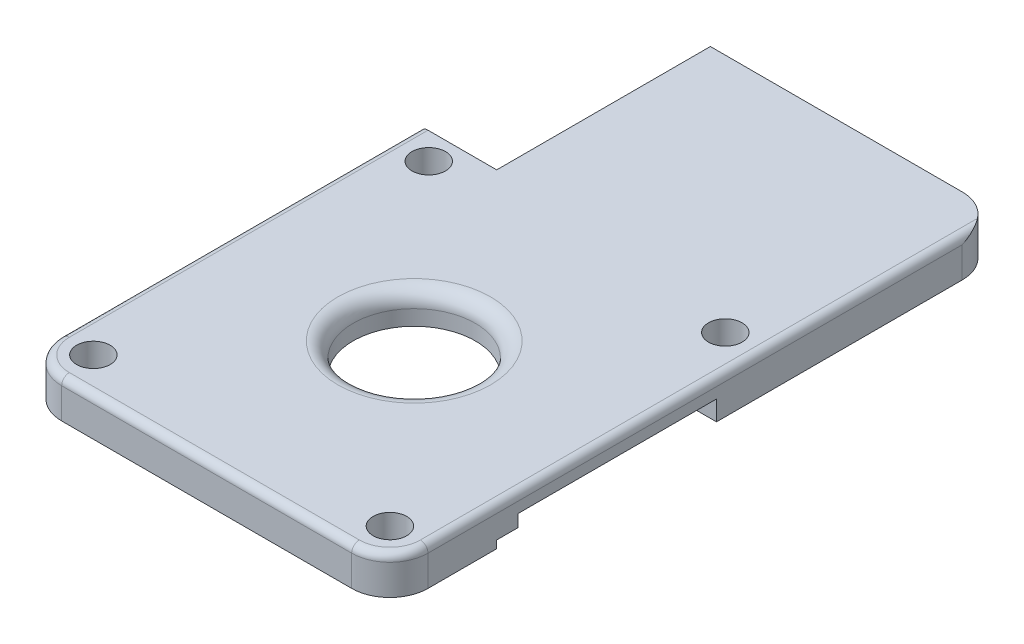
SolidWorks part; units mm, degrees
ref_plane "前视基准面" through (0, 0, 0) normal (0, 0, 1) x (1, 0, 0)
ref_plane "上视基准面" through (0, 0, 0) normal (0, 1, 0) x (1, 0, 0)
ref_plane "右视基准面" through (0, 0, 0) normal (1, 0, 0) x (0, 0, -1)
sketch "草图1" plane through (0, 0, 0) normal (0, 1, 0) x (1, 0, 0)
  line L0 (-12, 10.776) -> (-12, 24.224)
  line L18 (-9.5, 13.276) -> (9.5, 13.276) construction
  line L19 (-12, 10.776) -> (-12, -10.776)
  line L20 (-9.5, -13.276) -> (9.5, -13.276)
  line L21 (12, 10.776) -> (12, -10.776)
  line L22 (-12, 13.276) -> (12, -13.276) construction
  line L23 (-12, -13.276) -> (12, 13.276) construction
  line L24 (-9.5, 26.724) -> (9.5, 26.724)
  line L25 (12, 24.224) -> (12, 10.776)
  line L26 (-19.3805, 0) -> (19.2101, 0) construction
  line L27 (0, 33.0534) -> (0, -22.2948) construction
  line L37 (-9.715, 10.985) -> (9.715, -10.985) construction
  line L38 (-9.715, -10.985) -> (9.715, 10.985) construction
  line L39 (-9.714, 10.986) -> (9.714, 10.986) construction
  line L40 (-9.714, 10.986) -> (-9.714, -10.986) construction
  line L41 (-9.714, -10.986) -> (9.714, -10.986) construction
  line L42 (9.714, 10.986) -> (9.714, -10.986) construction
  line L43 (-9.714, 10.986) -> (9.714, -10.986) construction
  line L44 (-9.714, -10.986) -> (9.714, 10.986) construction
  arc A4 (-9.5, 13.276) -> (-12, 10.776) centre (-9.5, 10.776) ccw construction
  arc A5 (-9.5, -13.276) -> (-12, -10.776) centre (-9.5, -10.776) cw
  arc A6 (9.5, -13.276) -> (12, -10.776) centre (9.5, -10.776) ccw
  arc A7 (12, 10.776) -> (9.5, 13.276) centre (9.5, 10.776) ccw construction
  arc A8 (12, 24.224) -> (9.5, 26.724) centre (9.5, 24.224) ccw
  arc A9 (-12, 24.224) -> (-9.5, 26.724) centre (-9.5, 24.224) cw
  circle A12 centre (-9.714, -10.986) radius 2.2002
  circle A13 centre (-9.714, -10.986) radius 1.1
  circle A14 centre (9.714, -10.986) radius 1.1
  circle A15 centre (9.714, -10.986) radius 2.2002
  circle A16 centre (9.714, 10.986) radius 2.2002
  circle A17 centre (9.714, 10.986) radius 1.1
  circle A18 centre (-9.714, 10.986) radius 1.1
  circle A19 centre (-9.714, 10.986) radius 2.2002
  circle A20 centre (0, 0.32) radius 4
  point P0 (0, 0)
  point P28 (0, 0)
  point P34 (0, 0)
  dimension "D5" = 40
  dimension "D6" = 2.5
  dimension "D7" = 19.428
  dimension "D8" = 21.972
  dimension "D3" = 2.5
  dimension "D4" = 2.5
  dimension "D9" = 13.596
  dimension "D1" = 24
  dimension "D2" = 26.552
extrude "凸台-拉伸1" add sketch "草图1" against normal blind 2.5 contours A6 A15 L21 L25 A8 L24 A9 L0 L19 A5 A12 L20 A20 A16 A19 | A16 A17 | A19 A18 | A12 A13 | A15 A14
sketch "草图2" plane through (12, 0, 0) normal (1, 0, 0) x (0, 0, -1)
  line L0 (24.224, -2.5) -> (-10.776, -2.5) construction
  line L1 (-6.276, -2.5) -> (8.124, -2.5)
  line L2 (-6.276, -2.5) -> (-6.276, -2)
  line L3 (-6.276, -2) -> (8.124, -2)
  line L4 (8.124, -2.5) -> (8.124, -2)
  line L5 (-13.276, -2.5) -> (-13.276, 0) construction
  point P8 (8.124, -2.25)
  dimension "D1" = 21.4
  dimension "D2" = 7
  dimension "D3" = 0.5
extrude "切除-拉伸1" cut sketch "草图2" against normal through all
sketch "草图3" plane through (12, 0, 0) normal (1, 0, 0) x (0, 0, -1)
  line L0 (-13.276, -2.5) -> (-13.276, 0) construction
  line L1 (8.124, -2.5) -> (-4.876, -2.5)
  line L2 (8.124, -2.5) -> (8.124, -1.2)
  line L3 (8.124, -1.2) -> (-4.876, -1.2)
  line L4 (-4.876, -2.5) -> (-4.876, -1.2)
  dimension "D1" = 1.3
  dimension "D2" = 8.4
  dimension "D3" = 21.4
extrude "切除-拉伸2" cut sketch "草图3" against normal blind 4.5
sketch "草图4" plane through (-12, 0, 0) normal (-1, 0, 0) x (0, 0, 1)
  line L4 (-8.124, -2.5) -> (4.876, -2.5)
  line L5 (4.876, -2.5) -> (4.876, -1.2)
  line L6 (4.876, -1.2) -> (-8.124, -1.2)
  line L7 (-8.124, -1.2) -> (-8.124, -2.5)
  line L24 (-8.124, -2.5) -> (4.876, -2.5)
  line L25 (4.876, -2.5) -> (4.876, -1.2)
  line L26 (4.876, -1.2) -> (-8.124, -1.2)
  line L27 (-8.124, -1.2) -> (-8.124, -2.5)
  dimension "D2" = 0
extrude "切除-拉伸3" cut sketch "草图4" against normal blind 4.5 contours L24 L25 L26 L27
sketch "草图5" plane through (0, -2.5, 0) normal (0, -1, 0) x (1, 0, 0)
  line L0 (-12, -8.124) -> (12, -8.124) construction
  line L1 (-4, -8.124) -> (7.5, -8.124)
  line L2 (-4, -8.124) -> (-4, -25.424)
  line L3 (-4, -25.424) -> (7.5, -25.424)
  line L4 (7.5, -8.124) -> (7.5, -25.424)
  line L6 (7.5, -8.124) -> (7.5, 4.876) construction
  line L7 (12, -24.224) -> (12, -8.124) construction
  line L8 (-9.5, -26.724) -> (9.5, -26.724) construction
  dimension "D1" = 16
  dimension "D2" = 1.3
extrude "切除-拉伸11" cut sketch "草图5" against normal up to surface (0.5 mm away) contours L2 L1 L4 L3 up to face at (0, -2, 1.976)
sketch "草图6" plane through (0, -2, 0) normal (0, -1, 0) x (1, 0, 0)
  line L0 (-4, -8.124) -> (-4, -25.424) construction
  line L5 (-4, -8.124) -> (2, -8.124)
  line L6 (-4, -8.124) -> (-4, -18.124)
  line L7 (-4, -18.124) -> (2, -18.124)
  line L8 (2, -8.124) -> (2, -18.124)
  line L9 (-7.5, -8.124) -> (-4, -8.124) construction
  line L10 (12, -24.224) -> (12, -8.124) construction
  line L11 (-12, -8.124) -> (-4, -8.124) construction
  dimension "D1" = 10
  dimension "D2" = 10
extrude "切除-拉伸12" cut sketch "草图6" against normal blind 0.5
fillet "圆角1" radius 0.5 5 edges at (-11.2678, 0, 12.5438) (0, 0, 13.276) (11.2678, 0, 12.5438) (12, 0, -6.724) (-12, 0, -6.724)
fillet "圆角2" radius 1 1 edges at (0, 0, 3.68)
sketch "草图7" plane through (0, 0, 0) normal (0, 1, 0) x (1, 0, 0)
  line L6 (-12, -10.776) -> (-12, 24.224) construction
  line L7 (-12, 26.724) -> (-7.7, 26.724)
  line L8 (-12, 26.724) -> (-12, 13.424)
  line L9 (-12, 13.424) -> (-7.7, 13.424)
  line L10 (-7.7, 26.724) -> (-7.7, 13.424)
  line L11 (-9.5, 26.724) -> (9.5, 26.724) construction
  dimension "D1" = 4.3
  dimension "D2" = 13.3
extrude "切除-拉伸13" cut sketch "草图7" against normal through all
chamfer "倒角1" distance 1.5 angle 25 3 edges at (0.9, 0, -26.724) (-7.7, 0, -20.074) (-9.6, 0, -13.424)
